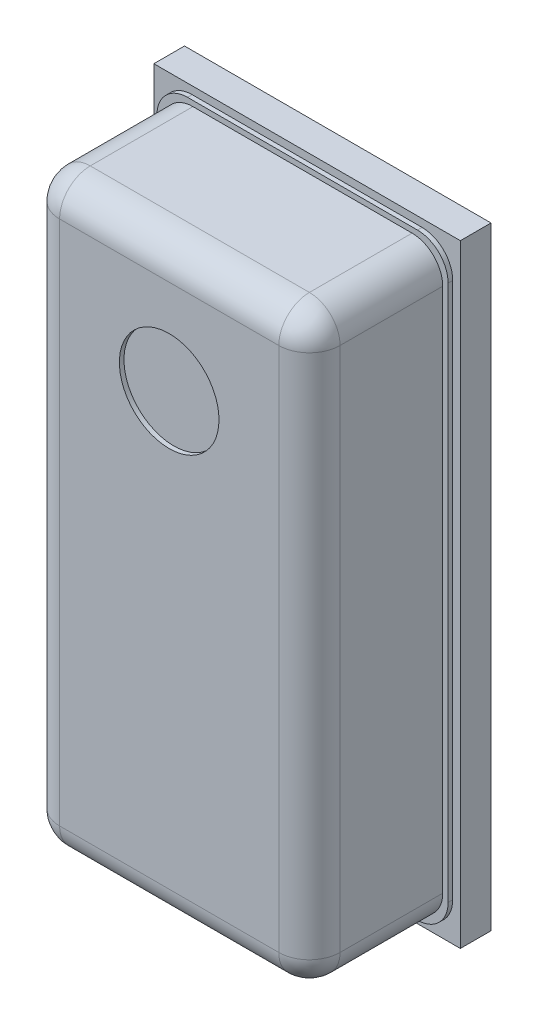
SolidWorks part; units mm, degrees
ref_plane "Plan de face" through (0, 0, 0) normal (0, 0, 1) x (1, 0, 0)
ref_plane "Plan de dessus" through (0, 0, 0) normal (0, 1, 0) x (1, 0, 0)
ref_plane "Plan de droite" through (0, 0, 0) normal (1, 0, 0) x (0, 0, -1)
sketch "Sketch1" plane through (0, 0, 0) normal (0, 0, 1) x (1, 0, 0)
  line L1 (-1, -2) -> (1, -2)
  line L2 (-1, -2) -> (-1, 2)
  line L3 (-1, 2) -> (1, 2)
  line L4 (1, -2) -> (1, 2)
  line L5 (-1, -2) -> (1, 2) construction
  line L6 (-1, 2) -> (1, -2) construction
  point P0 (0, 0)
  dimension "D1" = 4
  dimension "D2" = 2
extrude "Boss-Extrude1" add sketch "Sketch1" along normal blind 0.2
sketch "Sketch2" plane through (0, 0, 0) normal (0, 0, -1) x (-1, 0, 0)
  line L0 (0.3, 1.26) -> (0.3, 0.62)
  line L1 (-0.87, 1.26) -> (-0.3, 1.26)
  line L2 (-0.87, 1.26) -> (-0.87, 0.62)
  line L3 (-0.87, 0.62) -> (-0.3, 0.62)
  line L4 (-0.3, 1.26) -> (-0.3, 0.62)
  line L5 (-0.87, 1.26) -> (-0.3, 0.62) construction
  line L6 (-0.87, 0.62) -> (-0.3, 1.26) construction
  line L7 (0.3, 1.26) -> (0.87, 1.26)
  line L8 (0.87, 1.26) -> (0.87, 0.62)
  line L9 (0.3, 0.62) -> (0.87, 0.62)
  line L10 (0.3, 0.62) -> (0.87, 1.26) construction
  line L11 (0.3, 1.26) -> (0.87, 0.62) construction
  line L12 (0.3, 0.32) -> (0.3, -0.32)
  line L13 (0.3, 0.32) -> (0.87, 0.32)
  line L14 (0.87, 0.32) -> (0.87, -0.32)
  line L15 (0.3, -0.32) -> (0.87, -0.32)
  line L16 (0.3, -0.32) -> (0.87, 0.32) construction
  line L17 (0.3, 0.32) -> (0.87, -0.32) construction
  line L18 (0.3, -0.62) -> (0.3, -1.26)
  line L19 (0.3, -0.62) -> (0.87, -0.62)
  line L20 (0.87, -0.62) -> (0.87, -1.26)
  line L21 (0.3, -1.26) -> (0.87, -1.26)
  line L22 (0.3, -1.26) -> (0.87, -0.62) construction
  line L23 (0.3, -0.62) -> (0.87, -1.26) construction
  line L24 (-0.87, 0.32) -> (-0.87, -0.32)
  line L25 (-0.87, 0.32) -> (-0.3, 0.32)
  line L26 (-0.3, 0.32) -> (-0.3, -0.32)
  line L27 (-0.87, -0.32) -> (-0.3, -0.32)
  line L28 (-0.87, -0.32) -> (-0.3, 0.32) construction
  line L29 (-0.87, 0.32) -> (-0.3, -0.32) construction
  line L30 (-0.87, -0.62) -> (-0.87, -1.26)
  line L31 (-0.87, -0.62) -> (-0.619, -0.62)
  line L32 (-0.3, -0.939) -> (-0.3, -0.941)
  line L33 (-0.87, -1.26) -> (-0.619, -1.26)
  line L34 (-0.87, -1.26) -> (-0.3, -0.62) construction
  line L35 (-0.87, -0.62) -> (-0.3, -1.26) construction
  line L36 (-0.585, 0.94) -> (0.585, 0.94) construction
  line L37 (-0.585, 0.94) -> (-0.585, 0) construction
  line L38 (-0.3, -0.32) -> (0.3, 0.32) construction
  arc A0 (-0.3, -0.941) -> (-0.619, -1.26) centre (-0.619, -0.941) cw
  arc A1 (-0.619, -0.62) -> (-0.3, -0.939) centre (-0.619, -0.939) cw
  point P0 (-0.585, 0.94)
  point P5 (0, 0)
  point P6 (0.87, -0.62)
  point P8 (0.585, 0.94)
  point P13 (0.585, 0)
  point P18 (0.585, -0.94)
  point P23 (-0.585, 0)
  point P28 (-0.585, -0.94)
  dimension "D7" = 0.319
  dimension "D1" = 0.57
  dimension "D2" = 0.64
  dimension "D5" = 1.17
  dimension "D6" = 0.94
  dimension "D3" = 2
  dimension "D4" = 3
extrude "Boss-Extrude2" add sketch "Sketch2" along normal blind 0.01
sketch "Sketch3" plane through (0, 0, 0.2) normal (0, 0, 1) x (1, 0, 0)
  line L1 (-0.915, -1.915) -> (0.915, -1.915)
  line L2 (-0.915, -1.915) -> (-0.915, 1.915)
  line L3 (-0.915, 1.915) -> (0.915, 1.915)
  line L4 (0.915, -1.915) -> (0.915, 1.915)
  line L5 (-0.915, -1.915) -> (0.915, 1.915) construction
  line L6 (-0.915, 1.915) -> (0.915, -1.915) construction
  point P0 (0, 0)
  dimension "D1" = 1.83
  dimension "D2" = 3.83
extrude "Boss-Extrude3" add sketch "Sketch3" along normal offset from surface (0.9 mm away) 1.1 separate body up to face at (0, 0, 0)
fillet "Fillet1" radius 0.2 4 edges at (-0.915, 1.915, 0.65) (-0.915, -1.915, 0.65) (0.915, -1.915, 0.65) (0.915, 1.915, 0.65)
fillet "Fillet2" radius 0.2 8 edges at (0.8564, 1.8564, 1.1) (0, 1.915, 1.1) (-0.8564, 1.8564, 1.1) (-0.915, 0, 1.1) (-0.8564, -1.8564, 1.1) (0, -1.915, 1.1) (0.8564, -1.8564, 1.1) (0.915, 0, 1.1)
sketch "Sketch4" plane through (0, 0, 0.2) normal (0, 0, 1) x (1, 0, 0)
  line L0 (1, 2) -> (-1, 2) construction
  line L1 (-0.95, -1.95) -> (0.95, -1.95)
  line L2 (-0.95, -1.95) -> (-0.95, 1.95)
  line L3 (-0.95, 1.95) -> (0.95, 1.95)
  line L4 (0.95, -1.95) -> (0.95, 1.95)
  line L5 (-0.95, -1.95) -> (0.95, 1.95) construction
  line L6 (-0.95, 1.95) -> (0.95, -1.95) construction
  line L7 (1, -2) -> (1, 2) construction
  point P0 (0, 0)
  point P5 (0.9052, 1.8977)
  dimension "D1" = 0.05
  dimension "D2" = 0.05
extrude "Boss-Extrude4" add sketch "Sketch4" along normal blind 0.03
fillet "Fillet3" radius 0.2 4 edges at (-0.95, -1.95, 0.215) (-0.95, 1.95, 0.215) (0.95, 1.95, 0.215) (0.95, -1.95, 0.215)
shell "Shell1" thickness 0.03 removed face at (0, 0, 0.2)
sketch "Sketch5" plane through (0, 0, 1.1) normal (0, 0, 1) x (1, 0, 0)
  line L0 (1, 2) -> (-1, 2) construction
  circle A0 centre (0, 1.1) radius 0.325
  point P5 (0, 0)
  dimension "D1" = 0.9
  dimension "D2" = 0.65
extrude "Cut-Extrude2" cut sketch "Sketch5" against normal blind 0.03
sketch "Sketch6" plane through (0, 0, 0.2) normal (0, 0, 1) x (1, 0, 0)
  line L0 (0.885, 1.715) -> (0.885, -1.715) construction
  line L1 (0.715, -1.885) -> (-0.715, -1.885) construction
  line L2 (-0.885, -1.715) -> (-0.885, 1.715) construction
  line L3 (-0.715, 1.885) -> (0.715, 1.885) construction
  line L4 (0.885, 1.715) -> (0.885, -1.715)
  line L5 (0.715, -1.885) -> (-0.715, -1.885)
  line L6 (-0.885, -1.715) -> (-0.885, 1.715)
  line L7 (-0.715, 1.885) -> (0.715, 1.885)
  arc A0 (0.885, 1.715) -> (0.715, 1.885) centre (0.715, 1.715) ccw construction
  arc A1 (0.715, -1.885) -> (0.885, -1.715) centre (0.715, -1.715) ccw construction
  arc A2 (-0.885, -1.715) -> (-0.715, -1.885) centre (-0.715, -1.715) ccw construction
  arc A3 (-0.715, 1.885) -> (-0.885, 1.715) centre (-0.715, 1.715) ccw construction
  arc A4 (0.885, 1.715) -> (0.715, 1.885) centre (0.715, 1.715) ccw
  arc A5 (0.715, -1.885) -> (0.885, -1.715) centre (0.715, -1.715) ccw
  arc A6 (-0.885, -1.715) -> (-0.715, -1.885) centre (-0.715, -1.715) ccw
  arc A7 (-0.715, 1.885) -> (-0.885, 1.715) centre (-0.715, 1.715) ccw
extrude "Boss-Extrude5" add sketch "Sketch6" along normal blind 0.7 separate body
